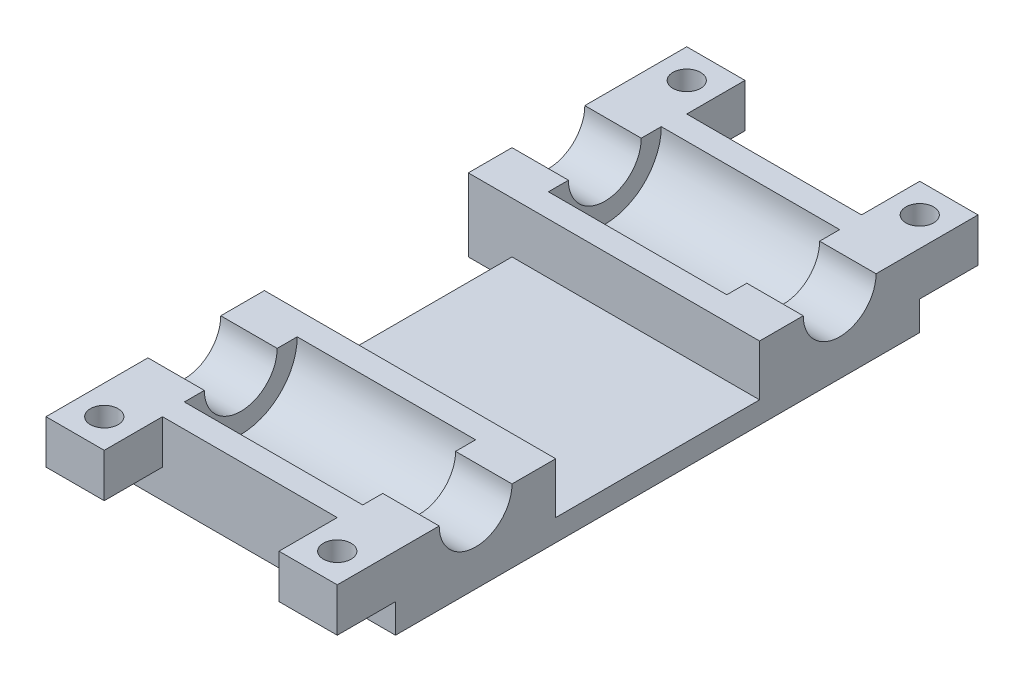
SolidWorks part; units mm, degrees
ref_plane "Front Plane" through (0, 0, 0) normal (0, 0, 1) x (1, 0, 0)
ref_plane "Top Plane" through (0, 0, 0) normal (0, 1, 0) x (1, 0, 0)
ref_plane "Right Plane" through (0, 0, 0) normal (1, 0, 0) x (0, 0, -1)
sketch "Sketch1" plane through (0, 0, 0) normal (0, 1, 0) x (1, 0, 0)
  line L1 (-20, 11) -> (20, 11)
  line L2 (-20, 11) -> (-20, -11)
  line L3 (-20, -11) -> (20, -11)
  line L4 (20, 11) -> (20, -11)
  line L5 (-20, 11) -> (20, -11) construction
  line L6 (-20, -11) -> (20, 11) construction
  point P0 (0, 0)
  dimension "D1" = 40
  dimension "D2" = 22
extrude "Boss-Extrude1" add sketch "Sketch1" along normal blind 11
sketch "Sketch2" plane through (0, 0, 0) normal (0, 1, 0) x (1, 0, 0)
  line L4 (20, -11) -> (20, 11)
  line L5 (-20, -11) -> (20, -11)
  line L6 (-20, 11) -> (-20, -11)
  line L7 (20, 11) -> (-20, 11)
  line L8 (20, -11) -> (20, 11)
  line L9 (-20, -11) -> (20, -11)
  line L10 (-20, 11) -> (-20, -11)
  line L11 (20, 11) -> (-20, 11)
  circle A0 centre (0, 0) radius 7.8438
  dimension "D1" = 0
extrude "Boss-Extrude2" add sketch "Sketch2" against normal blind 5
sketch "Sketch3" plane through (0, 11, 0) normal (0, 1, 0) x (1, 0, 0)
  line L1 (12.25, -7.75) -> (-12.25, -7.75)
  line L2 (12.25, -7.75) -> (12.25, 7.75)
  line L3 (12.25, 7.75) -> (-12.25, 7.75)
  line L4 (-12.25, -7.75) -> (-12.25, 7.75)
  line L5 (12.25, -7.75) -> (-12.25, 7.75) construction
  line L6 (12.25, 7.75) -> (-12.25, -7.75) construction
  point P0 (0, 0)
  dimension "D1" = 15.5
  dimension "D2" = 24.5
extrude "Cut-Extrude1" cut sketch "Sketch3" against normal blind 7.75
fillet "Fillet1" radius 7.75 2 edges at (0, 3.25, 7.75) (0, 3.25, -7.75)
sketch "Sketch4" plane through (-12.25, 0, 0) normal (1, 0, 0) x (0, 0, -1)
  line L0 (7.75, 11) -> (-7.75, 11) construction
  circle A0 centre (0, 11) radius 5
  dimension "D1" = 10
extrude "Cut-Extrude2" cut sketch "Sketch4" against normal through all both and the other way through all
sketch "Sketch5" plane through (0, 11, 0) normal (0, 1, 0) x (1, 0, 0)
  line L1 (20, -11) -> (12, -11)
  line L2 (20, -11) -> (20, -19)
  line L3 (20, -19) -> (12, -19)
  line L4 (12, -11) -> (12, -19)
  circle A0 centre (16, -15) radius 1.9058
  dimension "D1" = 8
  dimension "D2" = 8
  dimension "D3" = 4
  dimension "D4" = 4
extrude "Boss-Extrude3" add sketch "Sketch5" against normal blind 6
sketch "Sketch6" plane through (0, 5, 0) normal (0, -1, 0) x (1, 0, 0)
  line L4 (20, 11) -> (20, 19)
  line L5 (20, 19) -> (12, 19)
  line L6 (12, 19) -> (12, 11)
  line L7 (12, 11) -> (20, 11)
  line L8 (20, 11) -> (20, 19)
  line L9 (20, 19) -> (12, 19)
  line L10 (12, 19) -> (12, 11)
  line L11 (12, 11) -> (20, 11)
  circle A0 centre (16, 15) radius 1.9058 construction
  circle A1 centre (16, 15) radius 1.9058
  circle A2 centre (16, 15) radius 3
  circle M6 centre (16, 15) radius 1.9058
  dimension "D2" = 6
  dimension "D1" = 0
extrude "Cut-Extrude3" cut sketch "Sketch6" against normal blind 3 contours A2 M6
mirror "Mirror8" about plane through (0, 0, 0) normal (1, 0, 0) of "Cut-Extrude3", "Boss-Extrude3"
mirror "Mirror9" [suppressed] about plane through (0, 0, 0) normal (0, 0, 1)
chamfer "Chamfer2" [suppressed] distance 4 angle 45
ref_plane "Plane1" through (0, 0, -25) normal (0, 0, 1) x (1, 0, 0)
sketch "Sketch7" plane through (0, 0, -11) normal (0, 0, -1) x (-1, 0, 0)
  line L0 (-20, 11) -> (-20, -5) construction
  line L1 (-20, 1) -> (-4, 1)
  line L2 (-20, 1) -> (-20, 17.5)
  line L3 (-20, 17.5) -> (-4, 17.5)
  line L4 (-4, 1) -> (-4, 17.5)
  line L5 (-20, 11) -> (20, 11) construction
  dimension "D1" = 16
  dimension "D2" = 16.5
  dimension "D3" = 6.5
extrude "Boss-Extrude5" add sketch "Sketch7" along normal blind 28
mirror "Mirror14" about plane through (0, 0, -25) normal (0, 0, 1) of "Mirror8", "Cut-Extrude3", "Boss-Extrude3", "Cut-Extrude2", "Fillet1", "Cut-Extrude1", "Boss-Extrude2", "Boss-Extrude1"
sketch "Sketch9" plane through (4, 0, 0) normal (-1, 0, 0) x (0, 0, 1)
  line L0 (-39, 1) -> (-39, 11) construction
  line L1 (-11, 1) -> (-39, 1)
  line L2 (-11, 1) -> (-11, 4)
  line L3 (-11, 4) -> (-39, 4)
  line L4 (-39, 1) -> (-39, 4)
  dimension "D1" = 3
extrude "Boss-Extrude6" add sketch "Sketch9" along normal blind 18
sketch "Sketch10" plane through (0, 17.5, 0) normal (0, 1, 0) x (1, 0, 0)
  line L0 (-12.375, 25) -> (12.375, 25) construction
  line L1 (20, 39) -> (20, 11) construction
  line L3 (9, 23.75) -> (20, 23.75)
  line L4 (9, 23.75) -> (9, 26.25)
  line L5 (9, 26.25) -> (20, 26.25)
  line L6 (20, 23.75) -> (20, 26.25)
  circle A0 centre (9, 25) radius 3
  line M4 (20, 11) -> (20, 39)
  dimension "D3" = 6
  dimension "D1" = 0
  dimension "D2" = 11
  dimension "D4" = 2.5
  dimension "D5" = 1.25
extrude "Cut-Extrude4" cut sketch "Sketch10" against normal blind 10 contours L3 A0 L5 L4 | L5 A0 L3 L4 | A0 L3 L5 M4
sketch "Sketch11" plane through (0, 7.5, 0) normal (0, 1, 0) x (1, 0, 0)
  arc A0 (11.7272, 26.25) -> (11.7272, 23.75) centre (9, 25) ccw construction
  arc A1 (11.7272, 26.25) -> (11.7272, 23.75) centre (9, 25) ccw
  circle A2 centre (9, 25) radius 1.75
  point P4 (112.8504, -11.0766)
  dimension "D1" = 3.5
extrude "Cut-Extrude5" cut sketch "Sketch11" against normal through all both and the other way through all contours A2
sketch "Sketch12" plane through (4, 0, 0) normal (-1, 0, 0) x (0, 0, 1)
  line L1 (-39, 4) -> (-39, 11) construction
  circle A0 centre (-33, 11) radius 1.75
  dimension "D3" = 3.5
  dimension "D1" = 0
  dimension "D2" = 6
extrude "Cut-Extrude6" cut sketch "Sketch12" against normal through all both and the other way through all
sketch "Sketch15" plane through (20, 0, 0) normal (1, 0, 0) x (0, 0, -1)
  line L1 (33, 14.1754) -> (30.25, 12.5877)
  line L2 (30.25, 12.5877) -> (30.25, 9.4123)
  line L3 (30.25, 9.4123) -> (33, 7.8246)
  line L4 (33, 7.8246) -> (35.75, 9.4123)
  line L5 (35.75, 9.4123) -> (35.75, 12.5877)
  line L6 (35.75, 12.5877) -> (33, 14.1754)
  circle A0 centre (33, 11) radius 1.75 construction
  circle A1 centre (33, 11) radius 1.75
  circle A2 centre (33, 11) radius 2.75 construction
  dimension "D1" = 5.5
extrude "Cut-Extrude9" cut sketch "Sketch15" against normal blind 12 contours L1 L2 L3 L4 L5 L6
sketch "Sketch16" plane through (20, 0, 0) normal (1, 0, 0) x (0, 0, -1)
  line L1 (29, 11) -> (39, 11)
  line L2 (29, 11) -> (29, 17.5)
  line L3 (29, 17.5) -> (39, 17.5)
  line L4 (39, 11) -> (39, 17.5)
  circle A0 centre (33, 11) radius 1.75 construction
  circle A1 centre (33, 11) radius 1.75
  circle A2 centre (33, 11) radius 4
  dimension "D1" = 8
extrude "Cut-Extrude11" cut sketch "Sketch16" against normal blind 10
chamfer "Chamfer3" distance 2.5 angle 45 1 edges at (15, 11, -37)
fillet "Fillet2" radius 2 2 edges at (11.7272, 12.5, -23.75) (11.7272, 12.5, -26.25)
sketch "Sketch17" plane through (0, 4, 0) normal (0, 1, 0) x (1, 0, 0)
  line L4 (-14, 11) -> (20, 11)
  line L5 (-14, 39) -> (-14, 11)
  line L6 (20, 39) -> (-14, 39)
  line L7 (20, 11) -> (20, 39)
  line L8 (-14, 11) -> (20, 11)
  line L9 (-14, 39) -> (-14, 11)
  line L10 (20, 39) -> (-14, 39)
  line L11 (20, 11) -> (20, 39)
  dimension "D1" = 0
extrude "Cut-Extrude12" cut sketch "Sketch17" along normal through all
sketch "Sketch18" plane through (0, 4, 0) normal (0, 1, 0) x (1, 0, 0)
  circle A0 centre (9, 25) radius 1.75 construction
  circle A1 centre (9, 25) radius 1.75
extrude "Boss-Extrude7" add sketch "Sketch18" against normal up to surface (3 mm away) up to face at (9, 1, -23.25)
sketch "Sketch19" plane through (0, 8, 0) normal (0, -1, 0) x (1, 0, 0)
  line L0 (-20, -61) -> (-20, -69) construction
  line L1 (-20, -69) -> (-12, -69) construction
  line L2 (-12, -69) -> (-12, -61) construction
  line L3 (-12, -61) -> (-20, -61) construction
  line L4 (20, -69) -> (20, -61) construction
  line L5 (20, -61) -> (12, -61) construction
  line L6 (12, -61) -> (12, -69) construction
  line L7 (12, -69) -> (20, -69) construction
  line L8 (20, 11) -> (20, 19) construction
  line L9 (20, 19) -> (12, 19) construction
  line L10 (12, 19) -> (12, 11) construction
  line L11 (12, 11) -> (20, 11) construction
  line L12 (-20, 19) -> (-20, 11) construction
  line L13 (-20, 11) -> (-12, 11) construction
  line L14 (-12, 11) -> (-12, 19) construction
  line L15 (-12, 19) -> (-20, 19) construction
  line L16 (-20, -61) -> (-20, -69)
  line L17 (-20, -69) -> (-12, -69)
  line L18 (-12, -69) -> (-12, -61)
  line L19 (-12, -61) -> (-20, -61)
  line L20 (20, -69) -> (20, -61)
  line L21 (20, -61) -> (12, -61)
  line L22 (12, -61) -> (12, -69)
  line L23 (12, -69) -> (20, -69)
  line L24 (20, 11) -> (20, 19)
  line L25 (20, 19) -> (12, 19)
  line L26 (12, 19) -> (12, 11)
  line L27 (12, 11) -> (20, 11)
  line L28 (-20, 19) -> (-20, 11)
  line L29 (-20, 11) -> (-12, 11)
  line L30 (-12, 11) -> (-12, 19)
  line L31 (-12, 19) -> (-20, 19)
  circle A0 centre (-16, 15) radius 1.9058 construction
  circle A1 centre (16, 15) radius 1.9058 construction
  circle A2 centre (16, -65) radius 1.9058 construction
  circle A3 centre (-16, -65) radius 1.9058 construction
  circle A4 centre (-16, 15) radius 1.9058
  circle A5 centre (16, 15) radius 1.9058
  circle A6 centre (16, -65) radius 1.9058
  circle A7 centre (-16, -65) radius 1.9058
extrude "Boss-Extrude8" add sketch "Sketch19" along normal up to surface (3 mm away) up to face at (-16, 5, 12)
sketch "Sketch20" plane through (0, 5, 0) normal (0, -1, 0) x (1, 0, 0)
  line L1 (-12.8246, 15) -> (-14.4123, 17.75)
  line L2 (-14.4123, 17.75) -> (-17.5877, 17.75)
  line L3 (-17.5877, 17.75) -> (-19.1754, 15)
  line L4 (-19.1754, 15) -> (-17.5877, 12.25)
  line L5 (-17.5877, 12.25) -> (-14.4123, 12.25)
  line L6 (-14.4123, 12.25) -> (-12.8246, 15)
  line L7 (19.1754, 15) -> (17.5877, 17.75)
  line L8 (17.5877, 17.75) -> (14.4123, 17.75)
  line L9 (14.4123, 17.75) -> (12.8246, 15)
  line L10 (12.8246, 15) -> (14.4123, 12.25)
  line L11 (14.4123, 12.25) -> (17.5877, 12.25)
  line L12 (17.5877, 12.25) -> (19.1754, 15)
  line L13 (19.1754, -65) -> (17.5877, -62.25)
  line L14 (17.5877, -62.25) -> (14.4123, -62.25)
  line L15 (14.4123, -62.25) -> (12.8246, -65)
  line L16 (12.8246, -65) -> (14.4123, -67.75)
  line L17 (14.4123, -67.75) -> (17.5877, -67.75)
  line L18 (17.5877, -67.75) -> (19.1754, -65)
  line L19 (-12.8246, -65) -> (-14.4123, -62.25)
  line L20 (-14.4123, -62.25) -> (-17.5877, -62.25)
  line L21 (-17.5877, -62.25) -> (-19.1754, -65)
  line L22 (-19.1754, -65) -> (-17.5877, -67.75)
  line L23 (-17.5877, -67.75) -> (-14.4123, -67.75)
  line L24 (-14.4123, -67.75) -> (-12.8246, -65)
  circle A0 centre (-16, -65) radius 1.9058 construction
  circle A1 centre (16, -65) radius 1.9058 construction
  circle A2 centre (16, 15) radius 1.9058 construction
  circle A3 centre (-16, 15) radius 1.9058 construction
  circle A4 centre (-16, -65) radius 1.9058
  circle A5 centre (16, -65) radius 1.9058
  circle A6 centre (16, 15) radius 1.9058
  circle A7 centre (-16, 15) radius 1.9058
  circle A8 centre (-16, 15) radius 2.75 construction
  circle A9 centre (16, 15) radius 2.75 construction
  circle A10 centre (16, -65) radius 2.75 construction
  circle A11 centre (-16, -65) radius 2.75 construction
  dimension "D1" = 5.5
  dimension "D2" = 5.5
  dimension "D3" = 5.5
  dimension "D4" = 5.5
extrude "Cut-Extrude13" cut sketch "Sketch20" against normal blind 3
sketch "Sketch21" plane through (0, 1, 0) normal (0, -1, 0) x (1, 0, 0)
  line L0 (20, -39) -> (-20, -39) construction
  line L1 (-20, -39) -> (-20, -61) construction
  line L2 (-20, -61) -> (20, -61) construction
  line L3 (20, -61) -> (20, -39) construction
  line L4 (-20, -11) -> (20, -11) construction
  line L5 (20, -11) -> (20, 11) construction
  line L6 (20, 11) -> (-20, 11) construction
  line L7 (-20, 11) -> (-20, -11) construction
  line L8 (20, -39) -> (-20, -39)
  line L9 (-20, -39) -> (-20, -61)
  line L10 (-20, -61) -> (20, -61)
  line L11 (20, -61) -> (20, -39)
  line L12 (-20, -11) -> (20, -11)
  line L13 (20, -11) -> (20, 11)
  line L14 (20, 11) -> (-20, 11)
  line L15 (-20, 11) -> (-20, -11)
extrude "Cut-Extrude14" cut sketch "Sketch21" along normal through all
